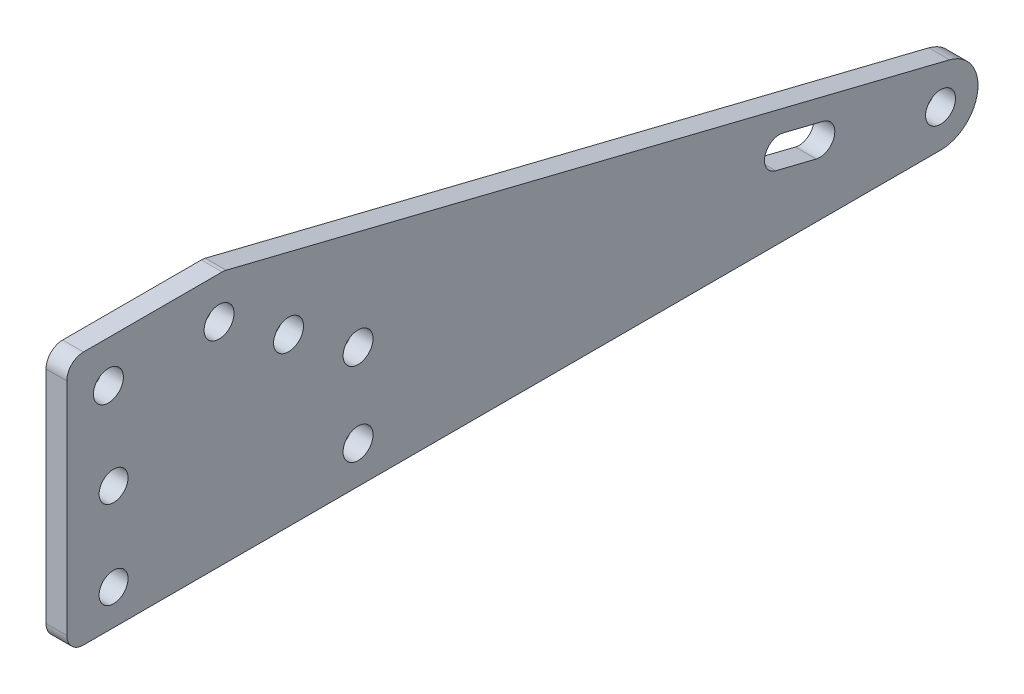
SolidWorks part; units mm, degrees
material "Acrylic (Medium-high impact)"
ref_plane "Front Plane" through (0, 0, 0) normal (0, 0, 1) x (1, 0, 0)
ref_plane "Top Plane" through (0, 0, 0) normal (0, 1, 0) x (1, 0, 0)
ref_plane "Right Plane" through (0, 0, 0) normal (1, 0, 0) x (0, 0, -1)
sketch "Sketch1" plane through (0, 0, 0) normal (1, 0, 0) x (0, 0, -1)
  line L0 (0, 6.35) -> (0, -6.35) construction
  line L1 (0, -6.35) -> (88.9, -6.35) construction
  line L2 (88.9, -6.35) -> (0, 6.35) construction
  line L3 (0, 6.35) -> (88.9, 6.35) construction
  line L4 (88.9, 6.35) -> (88.9, -6.35) construction
  line L5 (-20.1358, 26.5952) -> (90.2764, -0.8032)
  line L6 (0, -12.065) -> (88.9, -12.065)
  line L7 (-20.7475, 26.67) -> (-41.91, 26.67)
  line L8 (-44.45, 24.13) -> (-44.45, -9.525)
  line L9 (-41.91, -12.065) -> (0, -12.065)
  line L11 (0, 6.35) -> (-10.6066, 13.335) construction
  line L12 (-10.6066, 13.335) -> (-21.2132, 20.32) construction
  line L13 (-21.2132, 20.32) -> (-38.1, 20.32) construction
  circle A0 centre (0, 6.35) radius 2.286
  circle A1 centre (0, -6.35) radius 2.286
  circle A2 centre (88.9, -6.35) radius 2.286
  circle A3 centre (0, -6.35) radius 5.715 construction
  circle A4 centre (0, 6.35) radius 5.715 construction
  circle A5 centre (88.9, -6.35) radius 5.715 construction
  circle A6 centre (88.9, 6.35) radius 2.286 construction
  circle A7 centre (88.9, 6.35) radius 5.715 construction
  arc A8 (88.9, -12.065) -> (90.2764, -0.8032) centre (88.9, -6.35) ccw
  arc A9 (-20.7475, 26.67) -> (-20.1358, 26.5952) centre (-20.7475, 24.13) cw
  arc A10 (-44.45, -9.525) -> (-41.91, -12.065) centre (-41.91, -9.525) ccw
  arc A12 (-41.91, 26.67) -> (-44.45, 24.13) centre (-41.91, 24.13) ccw
  circle A13 centre (-21.2132, 20.32) radius 2.286
  circle A14 centre (-10.6066, 13.335) radius 2.286
  circle A15 centre (-38.1, 20.32) radius 2.286
  dimension "D1" = 4.572
  dimension "D4" = 11.43
  dimension "D5" = 2.54
  dimension "D7" = 6.35
  dimension "D9" = 32.385
  dimension "D11" = 6.35
  dimension "D2" = 12.7
  dimension "D3" = 88.9
  dimension "D6" = 44.45
  dimension "D8" = 6.35
  dimension "D10" = 12.7
extrude "Boss-Extrude1" add sketch "Sketch1" along normal blind 3.175
sketch "Sketch2" plane through (3.175, 0, 0) normal (1, 0, 0) x (0, 0, -1)
  line L0 (-35.1004, 12.065) -> (-44.45, 12.065) construction
  line L1 (-44.45, 24.13) -> (-44.45, -9.525) construction
  line L2 (-37.3103, 6.6801) -> (-37.3103, -6.6801) construction
  line L3 (-37.3103, 8.89) -> (-37.3103, 12.065) construction
  line L5 (-37.3103, -8.89) -> (-37.3103, -12.065) construction
  line L6 (-41.91, -12.065) -> (88.9, -12.065) construction
  line L7 (-35.1004, 12.065) -> (-35.1004, -12.065) construction
  line L8 (-39.5202, 12.065) -> (-39.5202, -12.065) construction
  line L9 (64.3105, 0.0135) -> (70.4736, -1.5158) construction
  line L10 (64.8611, 2.2322) -> (71.0241, 0.7029)
  line L11 (63.7599, -2.2052) -> (69.923, -3.7345)
  line L12 (90.2764, -0.8032) -> (-20.1358, 26.5952) construction
  circle A0 centre (-37.3103, 6.6801) radius 2.2099
  circle A1 centre (-37.3103, -6.6801) radius 2.2099
  circle A2 centre (0, -6.35) radius 2.286 construction
  arc A3 (64.8611, 2.2322) -> (63.7599, -2.2052) centre (64.3105, 0.0135) ccw
  arc A4 (69.923, -3.7345) -> (71.0241, 0.7029) centre (70.4736, -1.5158) ccw
  circle A5 centre (0, 6.35) radius 2.286 construction
  circle A6 centre (88.9, -6.35) radius 2.286 construction
  point P11 (67.392, -0.7512)
  dimension "D3" = 4.4198
  dimension "D1" = 3.175
  dimension "D2" = 35.1004
  dimension "D4" = 24.13
  dimension "D5" = 3.175
  dimension "D6" = 6.35
  dimension "D7" = 19.05
extrude "Cut-Extrude1" cut sketch "Sketch2" against normal through all
sketch "Sketch3" plane through (3.175, 0, 0) normal (1, 0, 0) x (0, 0, -1)
  line L0 (-41.275, 23.495) -> (-20.8251, 23.495) construction
  line L2 (-20.8251, 23.495) -> (88.9, -3.733) construction
  line L3 (88.9, -3.733) -> (88.9, -8.89) construction
  line L4 (88.9, -8.89) -> (-41.275, -8.89) construction
  line L5 (-41.275, -8.89) -> (-41.275, 23.495) construction
  line L6 (-44.45, 24.13) -> (-44.45, -9.525) construction
  line L9 (90.2764, -0.8032) -> (-20.1358, 26.5952) construction
  line L10 (-41.91, -12.065) -> (88.9, -12.065) construction
  line L11 (-20.7475, 26.67) -> (-41.91, 26.67) construction
  circle A0 centre (-37.3103, 6.6801) radius 5.461 construction
  circle A1 centre (-37.3103, -6.6801) radius 5.461 construction
  circle A2 centre (-10.6066, 13.335) radius 5.461 construction
  circle A3 centre (0, 6.35) radius 5.461 construction
  circle A4 centre (0, -6.35) radius 5.461 construction
  circle A5 centre (88.9, -6.35) radius 5.461 construction
  circle A6 centre (0, -6.35) radius 2.286 construction
  circle A7 centre (-21.2132, 20.32) radius 5.461 construction
  circle A8 centre (-21.2132, 20.32) radius 2.286 construction
  text T0 "6" font "Stencil" height 24.13
  point P8 (-31.3288, 26.67)
  point P14 (88.9, -6.35)
  dimension "D7" = 3.175
  dimension "D1" = 3.175
  dimension "D2" = 3.175
  dimension "D4" = 3.175
  dimension "D5" = 3.175
extrude "Cut-Extrude2" [suppressed] cut sketch "Sketch3" against normal through all
sketch "Sketch4" plane through (3.175, 0, 0) normal (1, 0, 0) x (0, 0, -1)
  line L0 (-41.275, 23.495) -> (-20.8251, 23.495) construction
  line L1 (-7.3953, 8.483) -> (-5.7259, 7.3836)
  line L2 (2.286, -0.9994) -> (2.286, 0.9994)
  line L3 (2.286, 11.7006) -> (2.286, 16.9482)
  line L4 (-2.286, 11.6673) -> (-2.286, 18.3979)
  line L5 (88.9, -3.733) -> (88.9, -8.89) construction
  line L6 (-41.275, -8.89) -> (-41.275, 23.495) construction
  line L7 (-4.8807, 12.3014) -> (-3.1835, 11.1837)
  line L8 (-13.8179, 18.187) -> (-15.4872, 19.2864)
  line L9 (-15.07, 22.0669) -> (-2.7681, 19.0142)
  line L10 (88.9, -8.89) -> (-41.275, -8.89) construction
  line L11 (88.9, -3.733) -> (88.9, -8.89) construction
  line L12 (-41.275, 14.7784) -> (-41.275, 11.7864)
  line L13 (-32.5584, 23.495) -> (-26.7548, 23.495)
  line L14 (5.6764, 7.9375) -> (36.674, 7.9375)
  line L15 (-12.9295, -8.89) -> (-5.7907, -8.89)
  line L16 (-2.286, 0.9994) -> (-2.286, -0.9994)
  line L17 (62.9952, -5.2867) -> (69.1583, -6.8161) construction
  line L18 (62.0245, -5.8577) -> (62.0245, -8.255)
  line L19 (76.7196, -0.7104) -> (83.8915, -2.4901)
  line L20 (62.6595, -8.89) -> (83.1093, -8.89)
  line L21 (62.8124, -5.2414) -> (69.1583, -6.8161)
  line L22 (20.9031, -8.89) -> (58.2145, -8.89)
  line L23 (-20.8251, 23.495) -> (88.9, -3.733) construction
  line L24 (5.6764, 4.7625) -> (46.0273, 4.7625)
  line L25 (3.0739, 17.5645) -> (36.8269, 9.1888)
  line L33 (0, 6.35) -> (5.6764, 6.35) construction
  line L34 (5.6764, 6.35) -> (5.6764, 7.9375) construction
  line L35 (5.6764, 6.35) -> (5.6764, 4.7625) construction
  line L36 (58.8495, 3.2273) -> (58.8495, -8.255)
  line L40 (5.9775, -8.8619) -> (46.2141, 3.5206)
  line L41 (58.0277, 3.8342) -> (20.7163, -7.6481)
  circle A0 centre (-37.3103, 6.6801) radius 5.461 construction
  circle A1 centre (-21.2132, 20.32) radius 5.461 construction
  arc A2 (62.0245, -5.8577) -> (62.8124, -5.2414) centre (62.6595, -5.8577) cw
  circle A4 centre (-38.1, 20.32) radius 5.461 construction
  circle A5 centre (-10.6066, 13.335) radius 5.461 construction
  circle A6 centre (88.9, -6.35) radius 5.461 construction
  arc A7 (-11.5416, 7.9546) -> (-8.0426, 8.5133) centre (-10.6066, 13.335) ccw
  circle A8 centre (-10.6066, 13.335) radius 2.286 construction
  circle A10 centre (0, -6.35) radius 5.461 construction
  circle A11 centre (0, 6.35) radius 5.461 construction
  circle A12 centre (0, 6.35) radius 2.286 construction
  arc A13 (-5.4424, 6.8009) -> (-5.7259, 7.3836) centre (-6.0752, 6.8533) ccw
  arc A14 (-40.2932, 11.2545) -> (-34.3002, 11.2366) centre (-37.3103, 6.6801) cw
  arc A15 (-26.1776, 22.5954) -> (-26.4174, 18.6651) centre (-21.2132, 20.32) ccw
  arc A16 (-26.7528, 17.8978) -> (-33.3843, 11.4781) centre (-20.7119, 5.0226) ccw
  arc A17 (-26.7548, 23.495) -> (-26.1776, 22.5954) centre (-26.7548, 22.86) cw
  arc A18 (-26.7528, 17.8978) -> (-26.4174, 18.6651) centre (-27.0225, 18.4727) ccw
  arc A19 (-33.3843, 11.4781) -> (-34.3002, 11.2366) centre (-33.9501, 11.7664) cw
  arc A20 (-41.275, 11.7864) -> (-40.2932, 11.2545) centre (-40.64, 11.7864) ccw
  arc A21 (-40.3754, 15.3556) -> (-33.1356, 22.5954) centre (-38.1, 20.32) ccw
  arc A22 (-12.2493, 7.1182) -> (-13.4861, -7.9493) centre (-29.7211, 0.9679) cw
  arc A23 (-5.4424, 6.8009) -> (-2.6167, 1.5567) centre (0, 6.35) ccw
  arc A24 (-2.6167, -1.5567) -> (-5.1875, -8.0566) centre (0, -6.35) ccw
  arc A25 (-8.0426, 8.5133) -> (-7.3953, 8.483) centre (-7.7445, 7.9527) cw
  arc A26 (2.6167, 1.5567) -> (5.0851, 4.359) centre (0, 6.35) ccw
  arc A27 (-13.4861, -7.9493) -> (-12.9295, -8.89) centre (-12.9295, -8.255) ccw
  arc A28 (-5.7907, -8.89) -> (-5.1875, -8.0566) centre (-5.7907, -8.255) ccw
  arc A29 (-2.286, -0.9994) -> (-2.6167, -1.5567) centre (-2.921, -0.9994) cw
  arc A30 (-2.6167, 1.5567) -> (-2.286, 0.9994) centre (-2.921, 0.9994) cw
  arc A31 (60.0475, 3.4267) -> (62.9952, -5.2867) centre (64.3105, 0.0135) ccw construction
  arc A32 (69.1583, -6.8161) -> (75.8377, -0.4916) centre (70.4736, -1.5158) ccw construction
  arc A33 (69.923, -3.7345) -> (71.0241, 0.7029) centre (70.4736, -1.5158) ccw construction
  arc A34 (64.8611, 2.2322) -> (63.7599, -2.2052) centre (64.3105, 0.0135) ccw construction
  arc A35 (75.9319, -1.3464) -> (69.1583, -6.8161) centre (70.4736, -1.5158) cw
  arc A36 (83.7125, -8.0566) -> (84.2762, -3.4443) centre (88.9, -6.35) cw
  arc A37 (62.0245, -8.255) -> (62.6595, -8.89) centre (62.6595, -8.255) ccw
  arc A38 (75.9319, -1.3464) -> (76.7196, -0.7104) centre (76.5666, -1.3267) cw
  arc A39 (84.2762, -3.4443) -> (83.8915, -2.4901) centre (83.7386, -3.1064) ccw
  arc A40 (83.1093, -8.89) -> (83.7125, -8.0566) centre (83.1093, -8.255) ccw
  arc A43 (5.1875, -8.0566) -> (2.6167, -1.5567) centre (0, -6.35) ccw
  arc A45 (2.6167, 11.1433) -> (2.286, 11.7006) centre (2.921, 11.7006) cw
  arc A48 (20.9031, -8.89) -> (20.7163, -7.6481) centre (20.9031, -8.255) cw
  arc A49 (3.0739, 17.5645) -> (2.286, 16.9482) centre (2.921, 16.9482) ccw
  arc A50 (2.286, 0.9994) -> (2.6167, 1.5567) centre (2.921, 0.9994) cw
  arc A52 (2.6167, -1.5567) -> (2.286, -0.9994) centre (2.921, -0.9994) cw
  arc A53 (-15.7708, 19.8691) -> (-15.8469, 21.3328) centre (-21.2132, 20.32) ccw
  arc A55 (-5.1642, 12.8841) -> (-13.1705, 18.1567) centre (-10.6066, 13.335) ccw
  arc A56 (-11.5416, 7.9546) -> (-12.2493, 7.1182) centre (-11.6503, 7.329) ccw
  arc A59 (-40.3754, 15.3556) -> (-41.275, 14.7784) centre (-40.64, 14.7784) ccw
  arc A60 (-33.1356, 22.5954) -> (-32.5584, 23.495) centre (-32.5584, 22.86) cw
  circle A61 centre (-38.1, 20.32) radius 2.286 construction
  arc A62 (-4.8807, 12.3014) -> (-5.1642, 12.8841) centre (-4.5314, 12.8317) cw
  arc A63 (-2.286, 18.3979) -> (-2.7681, 19.0142) centre (-2.921, 18.3979) ccw
  arc A64 (-15.8469, 21.3328) -> (-15.07, 22.0669) centre (-15.2229, 21.4506) cw
  arc A65 (-13.1705, 18.1567) -> (-13.8179, 18.187) centre (-13.4687, 18.7173) cw
  arc A66 (-15.4872, 19.2864) -> (-15.7708, 19.8691) centre (-15.138, 19.8167) cw
  arc A67 (-3.1835, 11.1837) -> (-2.286, 11.6673) centre (-2.865, 11.6673) ccw
  arc A68 (5.0851, 8.341) -> (2.6167, 11.1433) centre (0, 6.35) ccw
  arc A69 (5.6764, 4.7625) -> (5.0851, 4.359) centre (5.6764, 4.1275) ccw
  arc A71 (36.674, 7.9375) -> (36.8269, 9.1888) centre (36.674, 8.5725) ccw
  arc A72 (5.6764, 7.9375) -> (5.0851, 8.341) centre (5.6764, 8.5725) cw
  arc A75 (58.8495, -8.255) -> (58.2145, -8.89) centre (58.2145, -8.255) cw
  arc A76 (5.1875, -8.0566) -> (5.9775, -8.8619) centre (5.7907, -8.255) ccw
  arc A77 (46.0273, 4.7625) -> (46.2141, 3.5206) centre (46.0273, 4.1275) cw
  arc A78 (58.8495, 3.2273) -> (58.0277, 3.8342) centre (58.2145, 3.2273) ccw
  point P36 (-25.6564, 23.495)
  point P39 (-26.2182, 18.1354)
  point P42 (-33.7126, 10.7885)
  point P45 (-41.275, 10.4356)
  point P66 (-4.8343, -8.89)
  point P69 (-2.286, -1.3905)
  point P72 (-2.286, 1.3905)
  point P92 (-5.3993, 7.1685)
  point P126 (60.0475, 3.4267)
  point P131 (2.286, 17.76)
  point P134 (2.286, 1.3905)
  point P139 (2.286, -1.3905)
  point P175 (-5.2073, 12.5165)
  point P178 (-2.286, 18.8946)
  point P181 (-16.1361, 22.3314)
  point P184 (-13.4913, 17.9719)
  point P187 (-15.8139, 19.5015)
  point P202 (5.2252, 7.9375)
  dimension "D1" = 3.175
  dimension "D2" = 0.635
  dimension "D4" = 3.175
  dimension "D6" = 3.175
  dimension "D3" = 3.175
extrude "Cut-Extrude3" [suppressed] cut sketch "Sketch4" against normal through all
